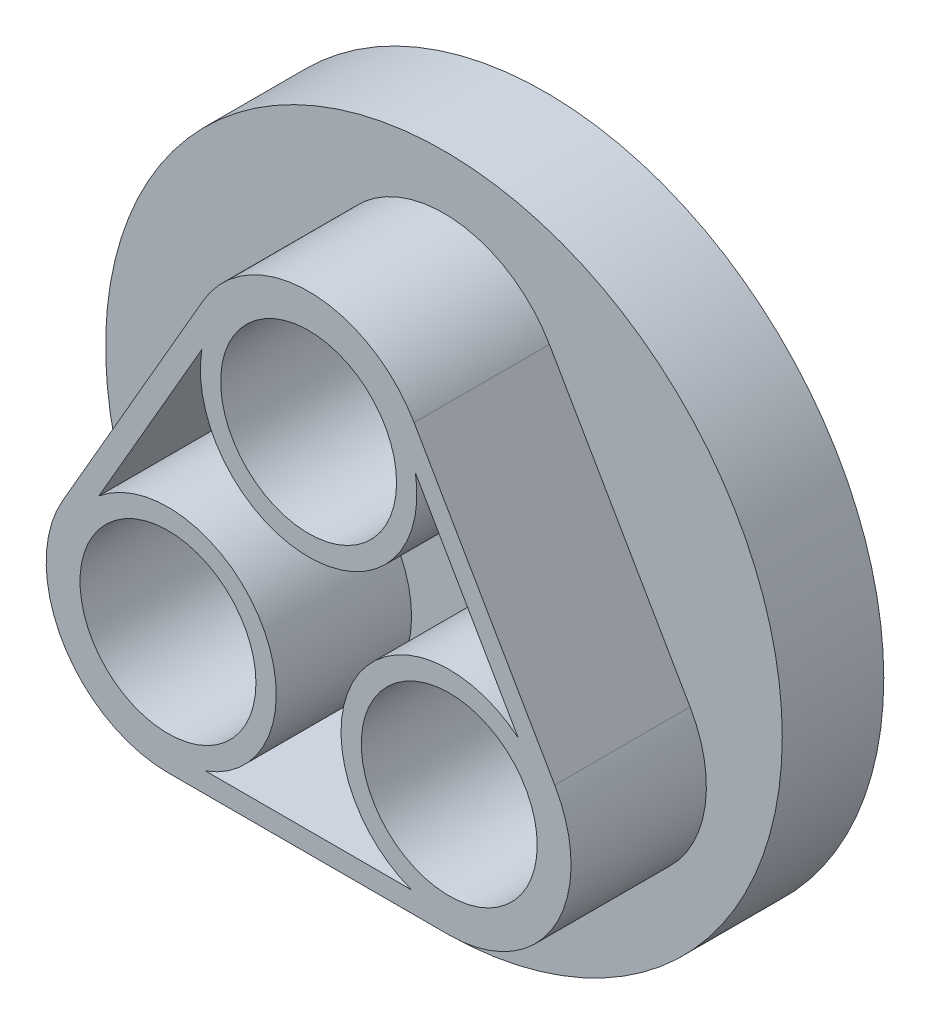
SolidWorks part; units mm, degrees
ref_plane "前基準面" through (0, 0, 0) normal (0, 0, 1) x (1, 0, 0)
ref_plane "上基準面" through (0, 0, 0) normal (0, 1, 0) x (1, 0, 0)
ref_plane "右基準面" through (0, 0, 0) normal (1, 0, 0) x (0, 0, -1)
sketch "草圖1" plane through (0, 0, 0) normal (0, 0, 1) x (1, 0, 0)
  circle A0 centre (0, 0) radius 50
  dimension "D1" = 100
extrude "填料-伸長1" add sketch "草圖1" along normal blind 15
shell "薄殼1" thickness 3 removed face at (50, 0, 0)
sketch "草圖2" plane through (0, 0, 15) normal (0, 0, 1) x (1, 0, 0)
  line L0 (-15.5885, 33) -> (-36.3731, -3)
  line L1 (-20.7846, -30) -> (20.7846, -30)
  line L2 (36.3731, -3) -> (15.5885, 33)
  circle A3 centre (0, 0) radius 24 construction
  arc A4 (-15.5885, 33) -> (15.5885, 33) centre (0, 24) cw
  arc A5 (36.3731, -3) -> (20.7846, -30) centre (20.7846, -12) cw
  arc A6 (-20.7846, -30) -> (-36.3731, -3) centre (-20.7846, -12) cw
  point P1 (0, 0)
  point P4 (0, 0)
  point P12 (0, 0)
  point P13 (0, 0)
  point P18 (0, 0)
  point P20 (0, 0)
  dimension "D2" = 48
  dimension "D5" = 18
  dimension "D4" = 3
extrude "填料-伸長2" add sketch "草圖2" along normal blind 20
sketch "草圖3" plane through (0, 0, 35) normal (0, 0, 1) x (1, 0, 0)
  circle A0 centre (0, 24) radius 13
  circle A1 centre (-20.7846, -12) radius 13
  circle A2 centre (20.7846, -12) radius 13
  dimension "D1" = 26
extrude "除料-伸長1" cut sketch "草圖3" against normal through all
sketch "草圖4" plane through (0, 0, 12) normal (0, 0, -1) x (-1, 0, 0)
  circle A0 centre (0, 24) radius 13
  circle A1 centre (0, 24) radius 16
  circle A2 centre (20.7846, -12) radius 16
  circle A3 centre (20.7846, -12) radius 13
  circle A4 centre (-20.7846, -12) radius 16
  circle A5 centre (-20.7846, -12) radius 13
  circle A6 centre (0, 0) radius 24 construction
  point P7 (0, 0)
  dimension "D1" = 26
  dimension "D4" = 48
  dimension "D2" = 3
  dimension "D3" = 3
extrude "填料-伸長3" add sketch "草圖4" along normal up to surface (12 mm away) up to face at (47, 0, 0)
shell "薄殼5" thickness 3 removed face at (13, 24, 35)
